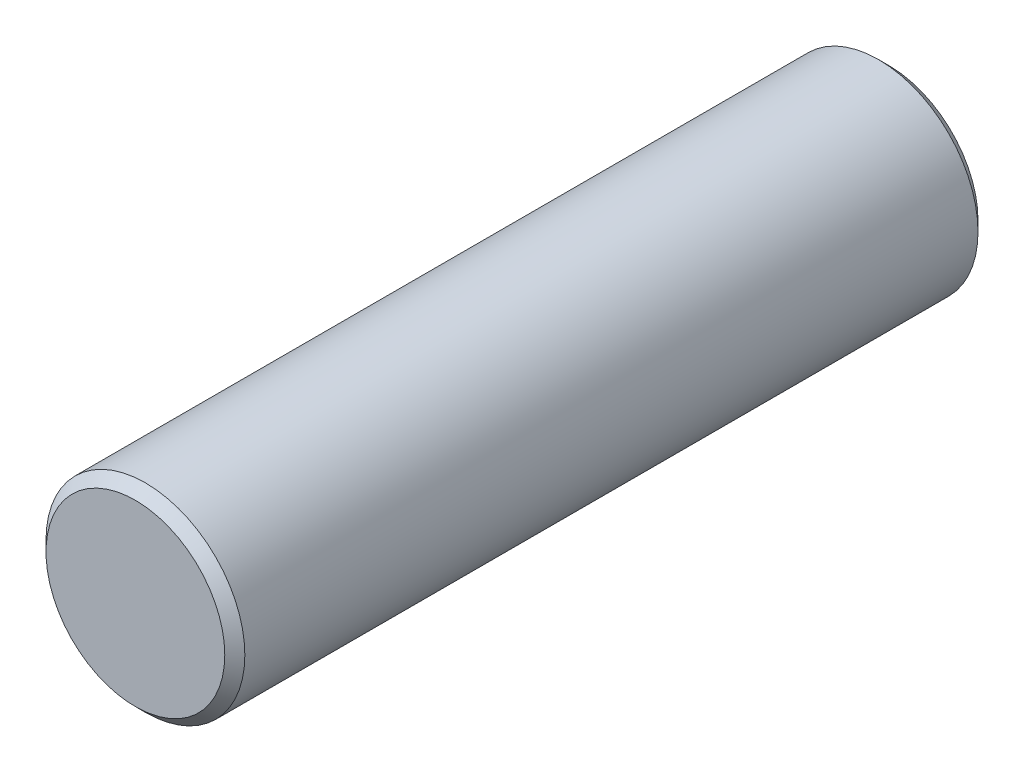
SolidWorks part; units mm, degrees
ref_plane "前视基准面" through (0, 0, 0) normal (0, 0, 1) x (1, 0, 0)
ref_plane "上视基准面" through (0, 0, 0) normal (0, 1, 0) x (1, 0, 0)
ref_plane "右视基准面" through (0, 0, 0) normal (1, 0, 0) x (0, 0, -1)
other "Configuration Table"
sketch "Sketch1" plane through (0, 0, 0) normal (0, 0, 1) x (1, 0, 0)
  circle A0 centre (0, 0) radius 9.9
extrude "Boss-Extrude1" add sketch "Sketch1" along normal blind 75
chamfer "Chamfer1" distance 1 angle 45 1 edges at (9.9, 0, 0)
chamfer "Chamfer2" distance 1 angle 45 1 edges at (9.9, 0, 75)
sketch3d "3DSketch1"
  line L0 (0, 0, 0) -> (0, 0, 75) construction
ref_axis "pin_axis" through (0, 0, 0) along (0, 0, 1)
